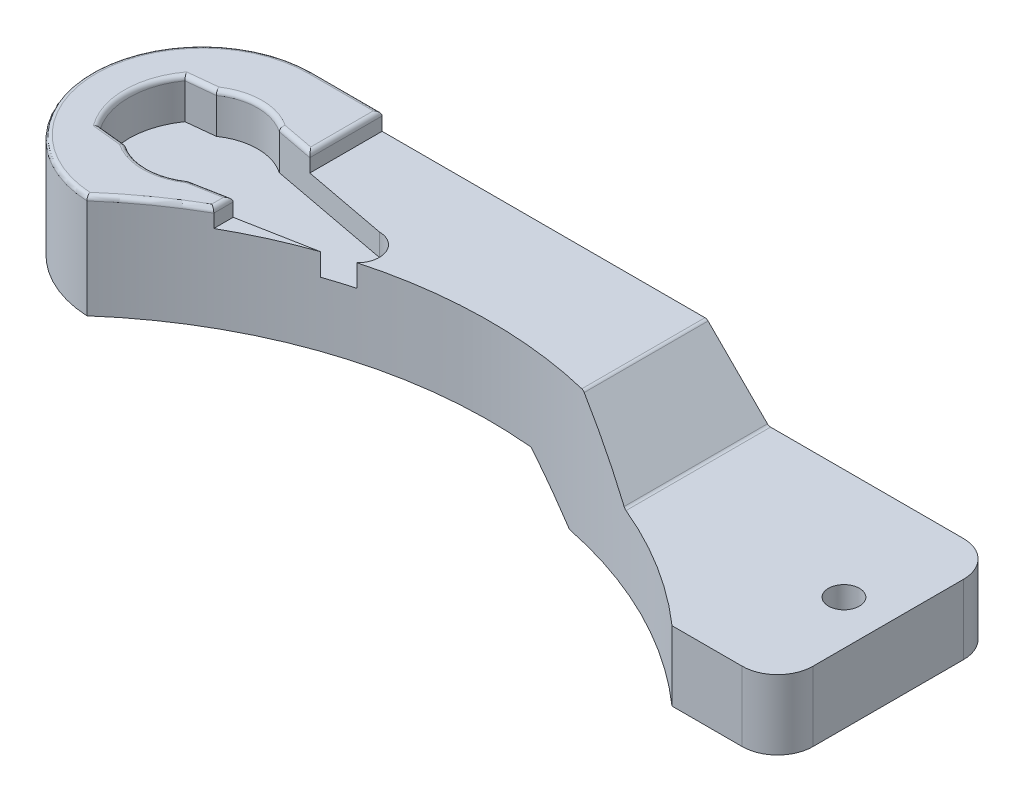
SolidWorks part; units mm, degrees
ref_plane "Front Plane" through (0, 0, 0) normal (0, 0, 1) x (1, 0, 0)
ref_plane "Top Plane" through (0, 0, 0) normal (0, 1, 0) x (1, 0, 0)
ref_plane "Right Plane" through (0, 0, 0) normal (1, 0, 0) x (0, 0, -1)
sketch "Sketch1" plane through (0, 0, 0) normal (0, 1, 0) x (1, 0, 0)
  line L1 (-45, 12.5) -> (45, 12.5)
  line L2 (-45, 12.5) -> (-45, -12.5)
  line L3 (-45, -12.5) -> (45, -12.5)
  line L4 (45, 12.5) -> (45, -12.5)
  dimension "D1" = 90
  dimension "D2" = 45
  dimension "D3" = 25
  dimension "D4" = 12.5
extrude "Boss-Extrude1" add sketch "Sketch1" along normal blind 16.87
sketch "Sketch3" plane through (0, 16.87, 0) normal (0, 1, 0) x (1, 0, 0)
  line L0 (-39.2721, 4.7988) -> (-36.061, 5.1363)
  line L5 (-45, 12.5) -> (-45, -12.5) construction
  line L6 (-45, -12.5) -> (45, -12.5) construction
  line L7 (-39.2721, -4.7988) -> (-36.061, -5.1363)
  line L9 (-28.939, 5.1363) -> (-15, 2.5)
  line L11 (-28.939, -5.1363) -> (-15, -2.5)
  arc A0 (-28.939, 5.1363) -> (-36.061, 5.1363) centre (-32.5, 0) ccw
  arc A1 (-15, -2.5) -> (-15, 2.5) centre (-15, 0) ccw
  arc A3 (-36.061, -5.1363) -> (-28.939, -5.1363) centre (-32.5, 0) ccw
  arc A4 (-39.2721, -4.7988) -> (-39.2721, 4.7988) centre (-32.5, 0) cw
  point P5 (-40.8, 0)
  dimension "D1" = 12.5
  dimension "D2" = 5
  dimension "D3" = 3.2111
  dimension "D14" = 8.3
  dimension "D4" = 3.2111
  dimension "D5" = 17.5
  dimension "D6" = 12.5
  dimension "D7" = 12.5
  dimension "D8" = 12.5
  dimension "D9" = 6.7721
  dimension "D10" = 6.7721
  dimension "D11" = 13.939
  dimension "D12" = 13.939
extrude "Cut-Extrude2" cut sketch "Sketch3" against normal blind 4.5
sketch "Esquisse2" plane through (0, 0, 12.5) normal (0, 0, 1) x (1, 0, 0)
  line L0 (10, 16.87) -> (19, 7.87)
  line L1 (45, 16.87) -> (10, 16.87)
  line L2 (45, 16.87) -> (45, 7.87)
  line L3 (45, 7.87) -> (10, 7.87)
  line L4 (10, 16.87) -> (10, 7.87)
  line L5 (-45, 0) -> (10, 0)
  line L8 (10, 0) -> (10, 7.87)
  line L9 (10, 0) -> (4.88, 5.12)
  line L10 (4.88, 5.12) -> (-45, 5.12)
  line L11 (-45, 5.12) -> (-45, 0)
  line M3 (-45, 0) -> (45, 0)
  line M4 (45, 0) -> (45, 16.87)
  line M5 (45, 16.87) -> (-45, 16.87)
  line M6 (-45, 16.87) -> (-45, 0)
  dimension "D1" = 35
  dimension "D2" = 9
  dimension "D3" = 45
  dimension "D4" = 45
  dimension "D5" = 2.75
extrude "Enlèv. mat.-Extru.1" cut sketch "Esquisse2" against normal blind 34 contours L8 M3 M6 | L4 L3 M5 M4 region at (29.6393, 12.5913, 12.5) region at (-18.7592, 2.5183, 12.5)
fillet "Fillet1" 2 edges at (-45, 10.995, 12.5) (-45, 10.995, -12.5) type full round first side face at (5.485, 7.465, 12.5) second side face at (5.485, 7.465, -12.5) middle face at (-45, 10.995, 0)
sketch "Esquisse5" plane through (0, 0, 0) normal (0, -1, 0) x (-1, 0, 0)
  line L0 (-45, -12.5) -> (-45, 12.5) construction
  circle A0 centre (-40, 0) radius 1.75
  dimension "D2" = 3.5
  dimension "D1" = 5
extrude "Enlèv. mat.-Extru.4" cut sketch "Esquisse5" against normal through all
fillet "Fillet3" radius 4 2 edges at (45, 3.935, -12.5) (45, 3.935, 12.5)
sketch "Sketch8" plane through (0, 16.87, 0) normal (0, 1, 0) x (1, 0, 0)
  line L1 (-24.6881, 14.1476) -> (13.3414, 14.1476)
  line L2 (-24.6881, 14.1476) -> (-24.6881, -6.796)
  line L3 (-24.6881, -6.796) -> (13.3414, -6.796)
  line L4 (13.3414, 14.1476) -> (13.3414, -6.796)
  dimension "D1" = 38.0295
  dimension "D2" = 20.9436
  dimension "D3" = 14.1476
  dimension "D4" = 24.6881
extrude "Cut-Extrude6" cut sketch "Sketch8" against normal blind 2
sketch "Esquisse17" plane through (0, 5.12, 0) normal (0, -1, 0) x (1, 0, 0)
  circle A0 centre (-32.5, 0) radius 6.45
  dimension "D1" = 12.9
extrude "Enlèv. mat.-Extru.7" cut sketch "Esquisse17" against normal blind 3.6
sketch "Esquisse18" plane through (0, 0, 0) normal (0, 1, 0) x (1, 0, 0)
  circle A0 centre (0, -50) radius 50
  dimension "D2" = 100
  dimension "D1" = 50
extrude "Enlèv. mat.-Extru.8" cut sketch "Esquisse18" against normal through all and the other way through all
fillet "Fillet4" radius 0.5 14 edges at (-28.5941, 16.87, -12.5) (19, 7.87, -4.3747) (12, 14.87, -5.5193) (-37.6665, 16.87, -4.9676) (-26.8136, 16.87, -4.7343) (-32.5, 16.87, -6.25) (-37.6665, 16.87, 4.9676) (-24.6881, 16.87, 5.4262) (-26.8136, 16.87, 4.7343) (-32.5, 16.87, 6.25) (-40.8, 16.87, 0) (-24.6881, 16.87, -8.4162) (-29.0267, 16.87, 9.2882) (-44.9969, 16.87, -0.279)
